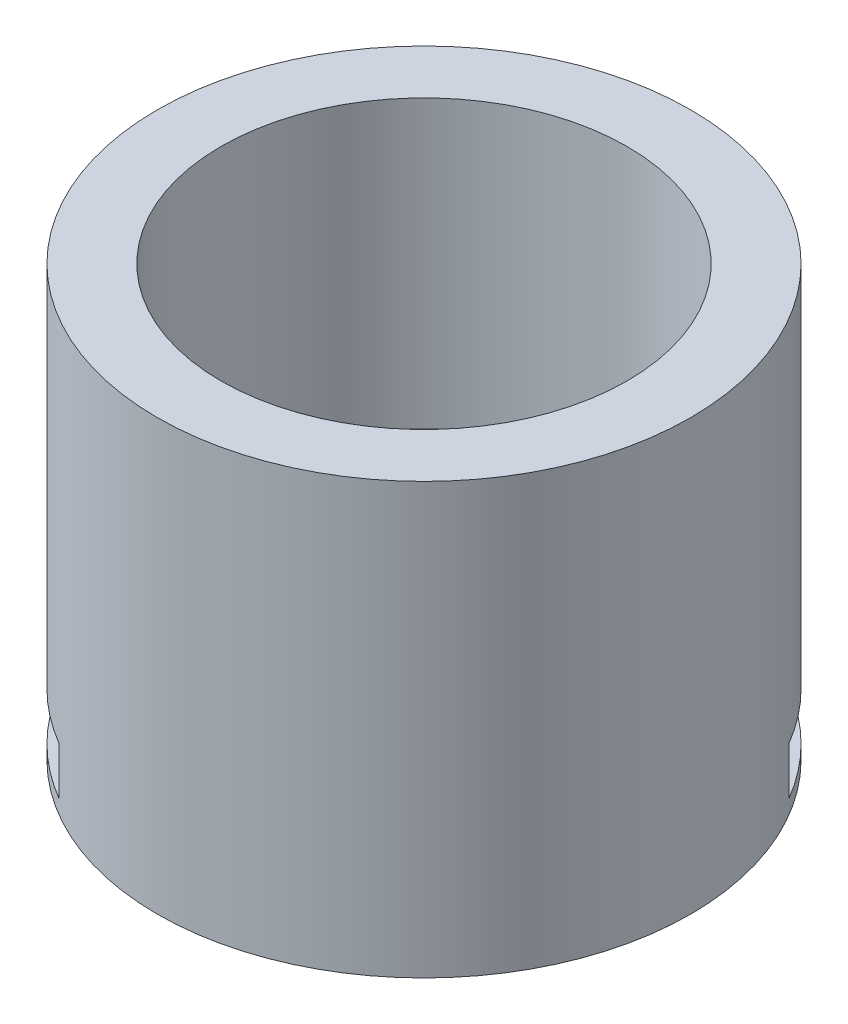
SolidWorks part; units mm, degrees
ref_plane "前视基准面" through (0, 0, 0) normal (0, 0, 1) x (1, 0, 0)
ref_plane "上视基准面" through (0, 0, 0) normal (0, 1, 0) x (1, 0, 0)
ref_plane "右视基准面" through (0, 0, 0) normal (1, 0, 0) x (0, 0, -1)
sketch "草图1" plane through (0, 0, 0) normal (0, 1, 0) x (1, 0, 0)
  circle A0 centre (0, 0) radius 27.9
  circle A1 centre (0, 0) radius 21.25 construction
  dimension "D1" = 55.8
  dimension "D2" = 42.5
extrude "凸台-拉伸1" add sketch "草图1" along normal blind 45 contours A0
sketch "草图2" plane through (0, 45, 0) normal (0, 1, 0) x (1, 0, 0)
  circle A0 centre (0, 0) radius 21.25
  dimension "D1" = 42.5
extrude "切除-拉伸1" cut sketch "草图2" against normal blind 30
sketch "草图3" plane through (0, 0, 0) normal (0, -1, 0) x (1, 0, 0)
  circle A0 centre (0, 0) radius 19 construction
  circle A1 centre (-19, 0) radius 1.25
  circle A2 centre (0, 19) radius 1.25
  circle A3 centre (19, 0) radius 1.25
  circle A4 centre (0, -19) radius 1.25
  point P14 (0, 0)
  dimension "D1" = 38
  dimension "D2" = 2.5
  dimension "D3" = 4
extrude "切除-拉伸2" cut sketch "草图3" against normal blind 6
ref_axis "基准轴1" through (0, 15, 0) along (0, 1, 0)
ref_plane "基准面2" through (0, 0, 0) normal (0.7071, 0, 0.7071) x (0, 1, 0)
ref_plane "基准面3" through (0, 0, 0) normal (0.7071, 0, -0.7071) x (0, 1, 0)
sketch "草图7" plane through (0, 0, 0) normal (0.7071, 0, -0.7071) x (0, 1, 0)
  line L0 (31.7266, 0) -> (-31.7266, 0) construction
  line L1 (6.5, -7) -> (1.5, -7)
  line L2 (6.5, -7) -> (6.5, 7)
  line L3 (6.5, 7) -> (1.5, 7)
  line L4 (1.5, -7) -> (1.5, 7)
  line L6 (0, 27.9) -> (0, -27.9) construction
  dimension "D1" = 7
  dimension "D2" = 14
  dimension "D3" = 5
  dimension "D4" = 1.5
extrude "切除-拉伸3" cut sketch "草图7" against normal mid plane 90 contours L1 L4 L3 L2
sketch "草图8" plane through (0, 0, 0) normal (0.7071, 0, 0.7071) x (0, 1, 0)
  line L0 (-32.5796, 0) -> (32.5796, 0) construction
  line L1 (8.5, 4.5) -> (1.5, 4.5)
  line L2 (8.5, 4.5) -> (8.5, -4.5)
  line L3 (8.5, -4.5) -> (1.5, -4.5)
  line L4 (1.5, 4.5) -> (1.5, -4.5)
  line L5 (0, 27.9) -> (0, -27.9) construction
  dimension "D1" = 7
  dimension "D2" = 9
  dimension "D3" = 4.5
  dimension "D4" = 1.5
extrude "切除-拉伸4" cut sketch "草图8" against normal blind 90 contours L2 L3 L4 L1
